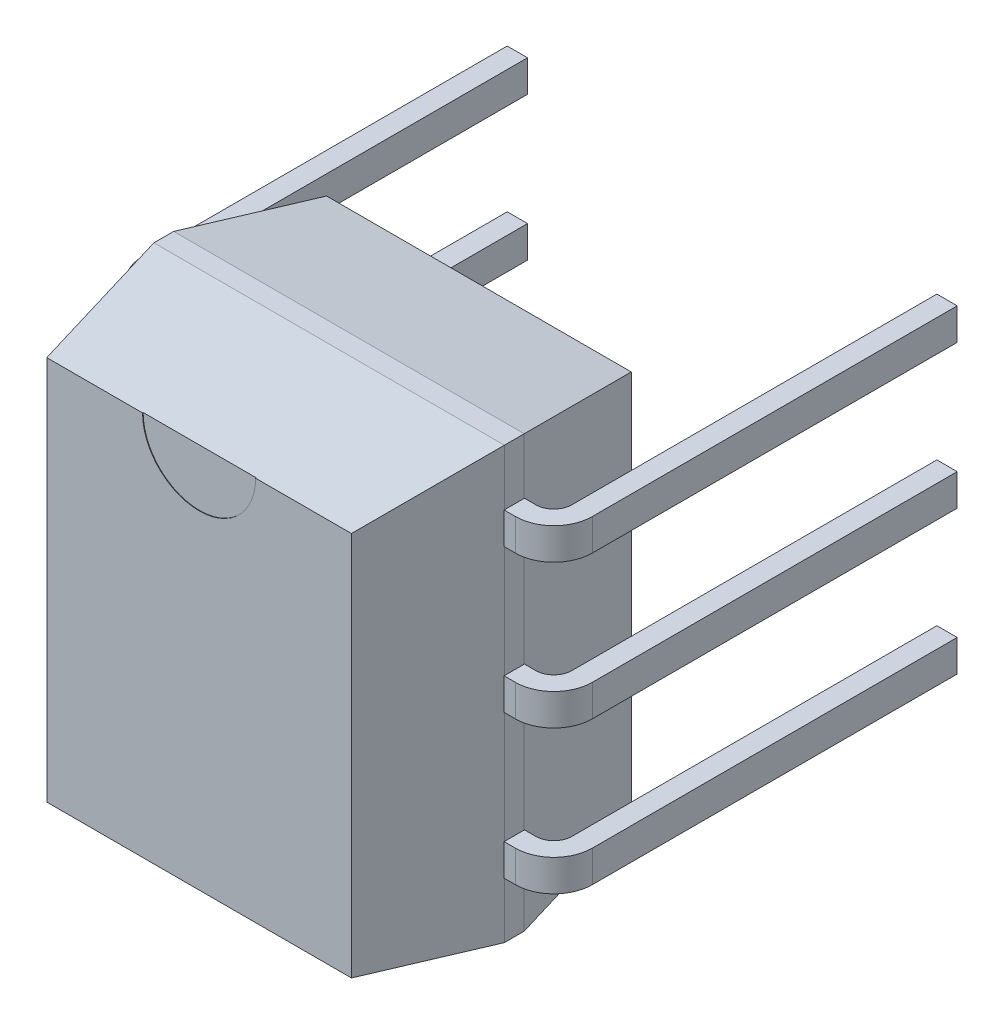
SolidWorks part; units mm, degrees
note: The reader was unsure of these and kept them because the rebuilt part matched: shared geometry of "Эскиз5<2>".
ref_plane "Front" through (0, 0, 0) normal (0, 0, 1) x (1, 0, 0)
ref_plane "Top" through (0, 0, 0) normal (0, 1, 0) x (1, 0, 0)
ref_plane "Right" through (0, 0, 0) normal (1, 0, 0) x (0, 0, -1)
sketch "Эскиз1" plane through (0, 0, 0) normal (0, 0, 1) x (1, 0, 0)
  line L1 (-0.8, -8.42) -> (0.8, -8.42)
  line L2 (-0.8, -8.42) -> (-0.8, -6.82)
  line L3 (-0.8, -6.82) -> (0.8, -6.82)
  line L4 (0.8, -8.42) -> (0.8, -6.82)
  line L5 (-0.8, -5.88) -> (0.8, -5.88)
  line L6 (-0.8, -5.88) -> (-0.8, -4.28)
  line L7 (-0.8, -4.28) -> (0.8, -4.28)
  line L8 (0.8, -5.88) -> (0.8, -4.28)
  line L9 (-0.8, -3.34) -> (0.8, -3.34)
  line L10 (-0.8, -3.34) -> (-0.8, -1.74)
  line L11 (-0.8, -1.74) -> (0.8, -1.74)
  line L12 (0.8, -3.34) -> (0.8, -1.74)
  line L13 (-0.8, -0.8) -> (0.8, -0.8)
  line L14 (-0.8, -0.8) -> (-0.8, 0.8)
  line L15 (-0.8, 0.8) -> (0.8, 0.8)
  line L16 (0.8, -0.8) -> (0.8, 0.8)
  line L17 (7.7, -8.42) -> (9.3, -8.42)
  line L18 (7.7, -8.42) -> (7.7, -6.82)
  line L19 (7.7, -6.82) -> (9.3, -6.82)
  line L20 (9.3, -8.42) -> (9.3, -6.82)
  line L21 (7.7, -5.88) -> (9.3, -5.88)
  line L22 (7.7, -5.88) -> (7.7, -4.28)
  line L23 (7.7, -4.28) -> (9.3, -4.28)
  line L24 (9.3, -5.88) -> (9.3, -4.28)
  line L25 (7.7, -3.34) -> (9.3, -3.34)
  line L26 (7.7, -3.34) -> (7.7, -1.74)
  line L27 (7.7, -1.74) -> (9.3, -1.74)
  line L28 (9.3, -3.34) -> (9.3, -1.74)
  line L29 (7.7, -0.8) -> (9.3, -0.8)
  line L30 (7.7, -0.8) -> (7.7, 0.8)
  line L31 (7.7, 0.8) -> (9.3, 0.8)
  line L32 (9.3, -0.8) -> (9.3, 0.8)
ref_plane "Плоскость1" through (0, 0, 5.33) normal (0, 0, 1) x (1, 0, 0)
sketch "Эскиз3" plane through (0, 0, 5.33) normal (0, 0, 1) x (1, 0, 0)
  line L0 (0.7, 1.27) -> (3.8, 1.27)
  line L1 (3.8, 1.27) -> (6.9, 1.27)
  line L2 (0.7, -8.89) -> (0.7, 1.27)
  line L3 (6.9, 1.27) -> (6.9, -8.89)
  line L4 (6.9, -8.89) -> (0.7, -8.89)
  line L5 (3.8, -8.89) -> (3.8, 1.27) construction
  dimension "D1" = 10.16
  dimension "D2" = 6.2
  dimension "D3" = 0.7
  dimension "D4" = 8.89
extrude "Вытянуть1" add sketch "Эскиз3" against normal blind 4.95
sketch "Эскиз4" plane through (0, 0, 0) normal (0, 1, 0) x (1, 0, 0)
  line L0 (0, 0) -> (0, -2.355)
  line L1 (0.5, -2.855) -> (0.7, -2.855)
  line L2 (0.7, -0.38) -> (0.7, -5.33) construction
  line L3 (3.8, -0.38) -> (3.8, -5.33) construction
  line L4 (6.9, -0.38) -> (0.7, -0.38) construction
  line L5 (6.9, -5.33) -> (0.7, -5.33) construction
  line L6 (7.1, -2.855) -> (6.9, -2.855)
  line L7 (7.6, 0) -> (7.6, -2.355)
  line L8 (0.7, -2.855) -> (6.9, -2.855)
  line L9 (7.6, 0) -> (7.6, 4.1)
  arc A0 (0, -2.355) -> (0.5, -2.855) centre (0.5, -2.355) ccw
  arc A1 (7.1, -2.855) -> (7.6, -2.355) centre (7.1, -2.355) ccw
  point P18 (0, -2.855)
  point P21 (7.6, -2.855)
  dimension "D2" = 0.5
  dimension "D1" = 4.1
sketch "Эскиз5" plane through (0, 0, 0) normal (0, 0, 1) x (1, 0, 0)
  line L0 (0.18, -2.26) -> (-0.18, -2.26)
  line L1 (0.18, 0.28) -> (-0.18, 0.28)
  line L2 (0.18, 0.28) -> (0.18, -0.28)
  line L3 (0.18, -0.28) -> (-0.18, -0.28)
  line L4 (-0.18, 0.28) -> (-0.18, -0.28)
  line L5 (0.18, -2.26) -> (0.18, -2.82)
  line L6 (0.18, -2.82) -> (-0.18, -2.82)
  line L7 (-0.18, -2.26) -> (-0.18, -2.82)
  line L8 (0.18, -4.8) -> (-0.18, -4.8)
  line L9 (0.18, -4.8) -> (0.18, -5.36)
  line L10 (0.18, -5.36) -> (-0.18, -5.36)
  line L11 (-0.18, -4.8) -> (-0.18, -5.36)
  line L12 (0.18, -7.34) -> (-0.18, -7.34)
  line L13 (0.18, -7.34) -> (0.18, -7.9)
  line L14 (0.18, -7.9) -> (-0.18, -7.9)
  line L15 (-0.18, -7.34) -> (-0.18, -7.9)
  dimension "D1" = 0.36
  dimension "D2" = 0.18
  dimension "D3" = 0.28
  dimension "D4" = 0.56
  dimension "D5" = 2.54
sweep "По траектории1" add profiles "Эскиз5" path "Эскиз4"
extrude "Вытянуть2" add sketch "Эскиз5<2>" against normal blind 4.1
sketch "Эскиз5<2>" plane through (0, 0, 0) normal (0, 0, 1) x (1, 0, 0) same geometry as "Эскиз5"
chamfer "Фаска1" distance 2.3 angle 10 8 edges at (3.8, -8.89, 0.38) (6.9, -3.81, 0.38) (3.8, 1.27, 0.38) (0.7, -3.81, 0.38) (3.8, 1.27, 5.33) (6.9, -3.81, 5.33) (3.8, -8.89, 5.33) (0.7, -3.81, 5.33)
sketch "Эскиз6" plane through (0, 0, 5.33) normal (0, 0, 1) x (1, 0, 0)
  line L0 (6.4944, 0.8644) -> (1.1056, 0.8644) construction
  circle A0 centre (3.8, 0.8644) radius 1
  dimension "D1" = 2
extrude "Вырез-Вытянуть1" cut sketch "Эскиз6" against normal blind 0.01
sketch "Эскиз7" plane through (0, 0, 5.33) normal (0, 0, 1) x (1, 0, 0)
  line L0 (6.9, -8.89) -> (0.7, -8.89) construction
  line L1 (-1.1745, -10.0023) -> (9.3817, -10.0023)
  line L2 (-1.1745, -10.0023) -> (-1.1745, -6.35)
  line L3 (-1.1745, -6.35) -> (9.3817, -6.35)
  line L4 (9.3817, -10.0023) -> (9.3817, -6.35)
  dimension "D1" = 2.54
extrude "Вырез-Вытянуть2" cut sketch "Эскиз7" against normal blind 20
chamfer "Фаска2" distance 2.3 angle 10 2 edges at (3.8, -6.35, 0.38) (3.8, -6.35, 5.33)
sketch "Эскиз8" plane through (0, 0, -4.1) normal (0, 0, -1) x (-1, 0, 0)
  circle A0 centre (0, 0) radius 0.1195
extrude "Вырез-Вытянуть3" cut sketch "Эскиз8" against normal blind 2
